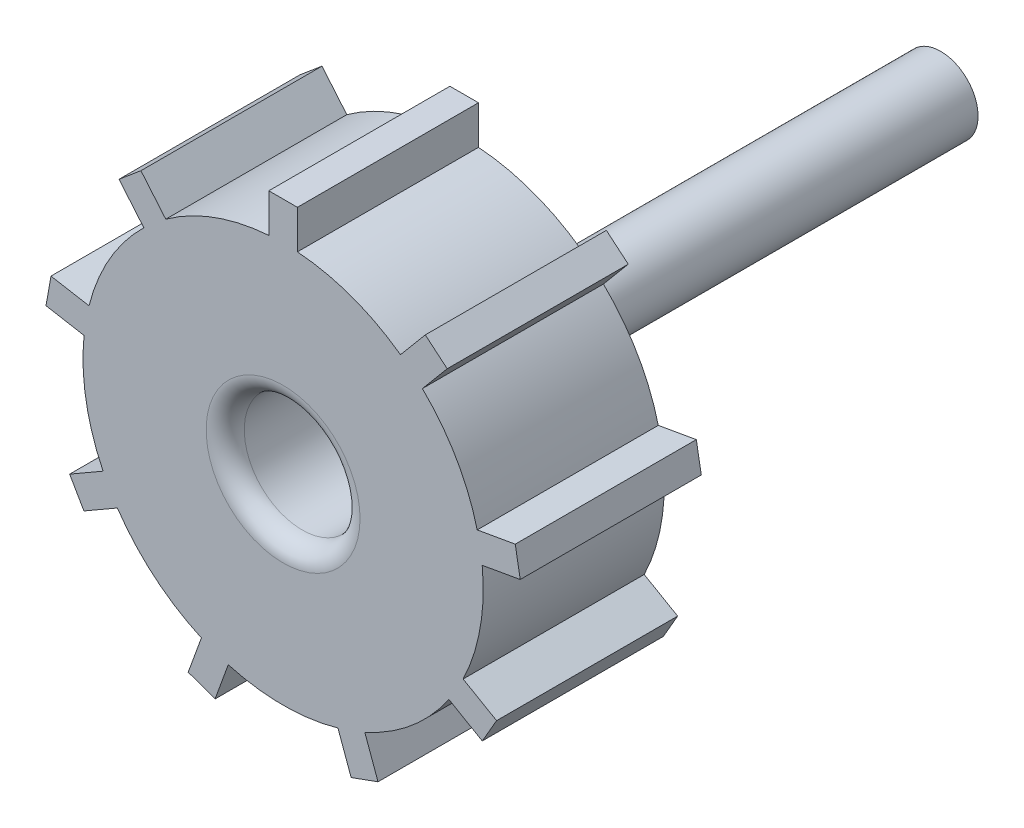
SolidWorks part; units mm, degrees
ref_plane "Ebene vorne" through (0, 0, 0) normal (0, 0, 1) x (1, 0, 0)
ref_plane "Ebene oben" through (0, 0, 0) normal (0, 1, 0) x (1, 0, 0)
ref_plane "Ebene rechts" through (0, 0, 0) normal (1, 0, 0) x (0, 0, -1)
sketch "Skizze1" plane through (0, 0, 0) normal (0, 0, 1) x (1, 0, 0)
  circle A0 centre (0, 0) radius 6
  dimension "D1" = 12
extrude "Aufsatz-Linear austragen1" add sketch "Skizze1" along normal blind 9
sketch "Skizze2" plane through (0, 0, 0) normal (0, 0, -1) x (-1, 0, 0)
  circle A0 centre (0, 0) radius 3.925
  dimension "D1" = 7.85
extrude "Aufsatz-Linear austragen2" add sketch "Skizze2" along normal blind 41
sketch "Skizze3" plane through (0, 0, 9) normal (0, 0, 1) x (1, 0, 0)
  circle A0 centre (0, 0) radius 21
  dimension "D1" = 42
extrude "Aufsatz-Linear austragen3" add sketch "Skizze3" along normal blind 19
sketch "Skizze4" plane through (0, 0, 28) normal (0, 0, 1) x (1, 0, 0)
  circle A0 centre (0, 0) radius 6.075
  dimension "D1" = 12.15
extrude "Schnitt-Linear austragen2" cut sketch "Skizze4" against normal blind 10
fillet "Verrundung1" radius 2 1 edges at (6.075, 0, 28)
sketch "Skizze5" plane through (0, 0, -41) normal (0, 0, -1) x (-1, 0, 0)
  circle A0 centre (0, 0) radius 1.5
  dimension "D1" = 3
extrude "Schnitt-Linear austragen3" cut sketch "Skizze5" against normal blind 15
sketch "Skizze6" plane through (0, 0, 28) normal (0, 0, 1) x (1, 0, 0)
  line L0 (0, 0) -> (0, 21) construction
  line L1 (0, 21) -> (0, 25) construction
  line L2 (-1.5, 25) -> (1.5, 25)
  line L3 (-1.5, 25) -> (-1.5, 20.9464)
  line L4 (1.5, 25) -> (1.5, 20.9464)
  circle A0 centre (0, 0) radius 21
  point P8 (0, 25)
  circle M3 centre (0, 0) radius 8.075
  circle M4 centre (0, 0) radius 21
  dimension "D2" = 42
  dimension "D1" = 4
  dimension "D3" = 3
extrude "Aufsatz-Linear austragen4" add sketch "Skizze6" against normal up to surface (19 mm away) contours L4 L2 L3 M4 | M4 M3 region at (0, 22.991, 28) region at (0, 20.406, 28) up to face at (6, 0, 9)
pattern_circular "Kreismuster1" count 9 over 360 about axis through (0, 0, 28) along (0, 0, -1) of "Aufsatz-Linear austragen4" reverse direction yes
